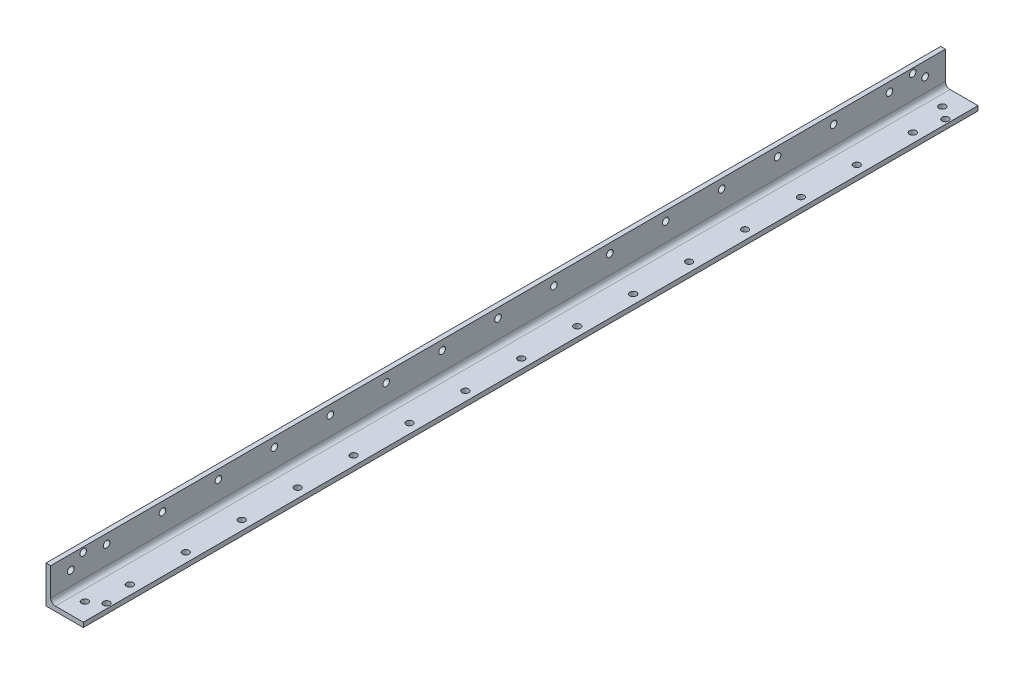
SolidWorks part; units mm, degrees
ref_plane "Front Plane" through (0, 0, 0) normal (0, 0, 1) x (1, 0, 0)
ref_plane "Top Plane" through (0, 0, 0) normal (0, 1, 0) x (1, 0, 0)
ref_plane "Right Plane" through (0, 0, 0) normal (1, 0, 0) x (0, 0, -1)
sketch "Sketch1" plane through (0, 0, 0) normal (0, 0, 1) x (1, 0, 0)
  line L0 (0, 25.4) -> (0, 0)
  line L1 (0, 0) -> (25.4, 0)
  line L2 (25.4, 0) -> (25.4, 3.175)
  line L3 (25.4, 3.175) -> (3.175, 3.175)
  line L4 (3.175, 3.175) -> (3.175, 25.4)
  line L5 (3.175, 25.4) -> (0, 25.4)
  dimension "D1" = 3.175
  dimension "D2" = 25.4
extrude "Boss-Extrude1" add sketch "Sketch1" along normal mid plane 609.6
fillet "Fillet1" radius 3.175 1 edges at (3.175, 3.175, 0)
sketch "Sketch2" plane through (0, 3.175, 0) normal (0, 1, 0) x (1, 0, 0)
  line L0 (25.4, -304.8) -> (25.4, 304.8) construction
  line L1 (25.4, 304.8) -> (6.35, 304.8) construction
  line L2 (0, 0) -> (25.4, 0) construction
  line L3 (0, -304.8) -> (0, 304.8) construction
  line L4 (25.4, -304.8) -> (6.35, -304.8) construction
  circle A0 centre (22.225, 285.75) radius 2.25
  circle A1 centre (13.7583, 292.1) radius 2.25
  circle A2 centre (22.225, -285.75) radius 2.25
  circle A3 centre (13.7583, -292.1) radius 2.25
  circle A4 centre (19.05, -266.7) radius 2.25
  circle A5 centre (19.05, -228.6) radius 2.25
  circle A6 centre (19.05, -190.5) radius 2.25
  circle A7 centre (19.05, -152.4) radius 2.25
  circle A8 centre (19.05, -114.3) radius 2.25
  circle A9 centre (19.05, -76.2) radius 2.25
  circle A10 centre (19.05, -38.1) radius 2.25
  circle A11 centre (19.05, 0) radius 2.25
  circle A12 centre (19.05, 38.1) radius 2.25
  circle A13 centre (19.05, 76.2) radius 2.25
  circle A14 centre (19.05, 114.3) radius 2.25
  circle A15 centre (19.05, 152.4) radius 2.25
  circle A16 centre (19.05, 190.5) radius 2.25
  circle A17 centre (19.05, 228.6) radius 2.25
  circle A18 centre (19.05, 266.7) radius 2.25
  dimension "D1" = 3.175
  dimension "D5" = 4.5
  dimension "D6" = 6.35
  dimension "D2" = 11.6417
  dimension "D3" = 12.7
  dimension "D4" = 6.35
  dimension "D7" = 38.1
  dimension "D8" = 15
  dimension "D9" = 38.1
extrude "Cut-Extrude1" cut sketch "Sketch2" against normal through all contours A3 | A2 | A1 | A0 region at (22.225, 3.175, -285.75) region at (13.7583, 3.175, -292.1) region at (22.225, 3.175, 285.75) region at (13.7583, 3.175, 292.1)
extrude "Cut-Extrude2" cut sketch "Sketch2<3>" against normal through all contours A4 | A5 | A6 | A7 | A8 | A9 | A10 | A11 L2 | L2 A11 | A12 | A13 | A14 | A15 | A16 | A17 | A18 region at (19.05, 3.175, -0.9549) region at (19.05, 3.175, 0.9549) region at (19.05, 3.175, 266.7) region at (19.05, 3.175, 228.6) region at (19.05, 3.175, 190.5) region at (19.05, 3.175, 152.4) region at (19.05, 3.175, 114.3) region at (19.05, 3.175, 76.2) region at (19.05, 3.175, 38.1) region at (19.05, 3.175, -38.1) region at (19.05, 3.175, -76.2) region at (19.05, 3.175, -114.3) region at (19.05, 3.175, -152.4) region at (19.05, 3.175, -190.5) region at (19.05, 3.175, -228.6) region at (19.05, 3.175, -266.7)
sketch "Sketch2<3>" plane through (0, 3.175, 0) normal (0, 1, 0) x (1, 0, 0) same geometry as "Sketch2"
ref_plane "Plane1" through (0, 0, 0) normal (-0.7071, 0.7071, 0) x (0, 0, -1)
mirror "Mirror1" about plane through (0, 0, 0) normal (-0.7071, 0.7071, 0) of "Cut-Extrude2"
sketch "Sketch3" plane through (3.175, 0, 0) normal (1, 0, 0) x (0, 0, -1)
  line L0 (-304.8, 6.35) -> (-304.8, 25.4) construction
  line L1 (-304.8, 25.4) -> (304.8, 25.4) construction
  line L2 (0, 0) -> (0, 25.4) construction
  line L3 (-268.95, 0) -> (-264.45, 0) construction
  circle A0 centre (-282.575, 22.225) radius 2.25
  circle A1 centre (-291.0417, 15.875) radius 2.25
  circle A2 centre (291.0417, 15.875) radius 2.25
  circle A3 centre (282.575, 22.225) radius 2.25
  dimension "D1" = 13.7583
  dimension "D5" = 4.5
  dimension "D2" = 8.4667
  dimension "D3" = 3.175
  dimension "D4" = 6.35
extrude "Cut-Extrude3" cut sketch "Sketch3" against normal through all
